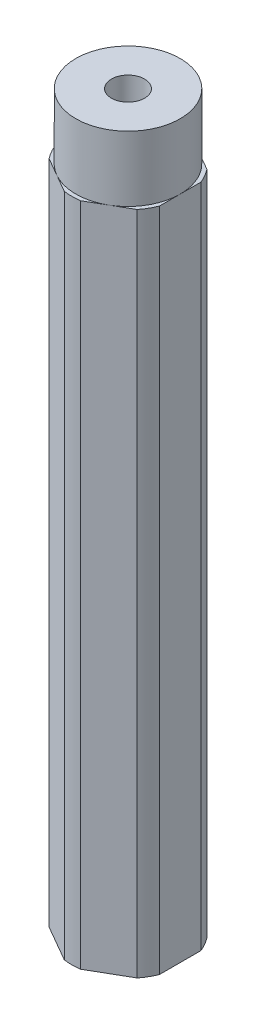
SolidWorks part; units mm, degrees
material "7075-T6 (SN)"
ref_plane "Front Plane" through (0, 0, 0) normal (0, 0, 1) x (1, 0, 0)
ref_plane "Top Plane" through (0, 0, 0) normal (0, 1, 0) x (1, 0, 0)
ref_plane "Right Plane" through (0, 0, 0) normal (1, 0, 0) x (0, 0, -1)
sketch "Sketch1" plane through (0, 0, 0) normal (0, 1, 0) x (1, 0, 0)
  line L1 (0, 7.3323) -> (-6.35, 3.6662)
  line L2 (-6.35, 3.6662) -> (-6.35, -3.6662)
  line L3 (-6.35, -3.6662) -> (0, -7.3323)
  line L4 (0, -7.3323) -> (6.35, -3.6662)
  line L5 (6.35, -3.6662) -> (6.35, 3.6662)
  line L6 (6.35, 3.6662) -> (0, 7.3323)
  circle A0 centre (0, 0) radius 6.35 construction
  circle A1 centre (0, 0) radius 6.8326
  dimension "D1" = 12.7
  dimension "D2" = 13.6652
extrude "Boss-Extrude1" add sketch "Sketch1" along normal mid plane 80.9625 contours L4 A1 L5 L6 L1 L2 L3 region at (0, 0, 0)
sketch "Sketch3" plane through (0, 40.4812, 0) normal (0, 1, 0) x (1, 0, 0)
  line L0 (5.3594, 4.2381) -> (0.9906, 6.7604) construction
  circle A0 centre (0, 0) radius 6.35
extrude "Boss-Extrude2" add sketch "Sketch3" along normal blind 7.9375
hole_wizard "#10-32 Tapped Hole1" positions "Sketch4" profile "Sketch5" tap size "#10-32" standard "ANSI Inch"
sketch "Sketch4" plane through (0, -40.4812, 0) normal (0, -1, 0) x (-1, 0, 0)
  point P0 (0, 0)
sketch "Sketch5" plane through (0, -40.4812, 0) normal (1, 0, 0) x (0, 0, -1)
  line L0 (0, 0) -> (0, 13.2428)
  line L1 (0, 13.2428) -> (2.0193, 12.0294)
  line L2 (2.0193, 12.0294) -> (2.0193, 0)
  line L5 (2.0193, 0) -> (0, 0)
  line L10 (0, 13.2428) -> (-2.0193, 12.0294) construction
  line L11 (0, -6.35) -> (0, 107.95) construction
  dimension "Tap Drill Dia." = 4.0386
  dimension "Tap Drill Depth" = 12.0294
  dimension "Drill Angle" = 118
cosmetic thread "Hole Thread1" parameters "D1"=9.652, "D2"=5.0386
sketch "Sketch2" plane through (0, -40.4812, 0) normal (0, 1, 0) x (1, 0, 0)
  circle A0 centre (0, 0) radius 2.0193
  dimension "D1" = 4.0386
extrude "Cut-Extrude1" cut sketch "Sketch2" along normal through all
